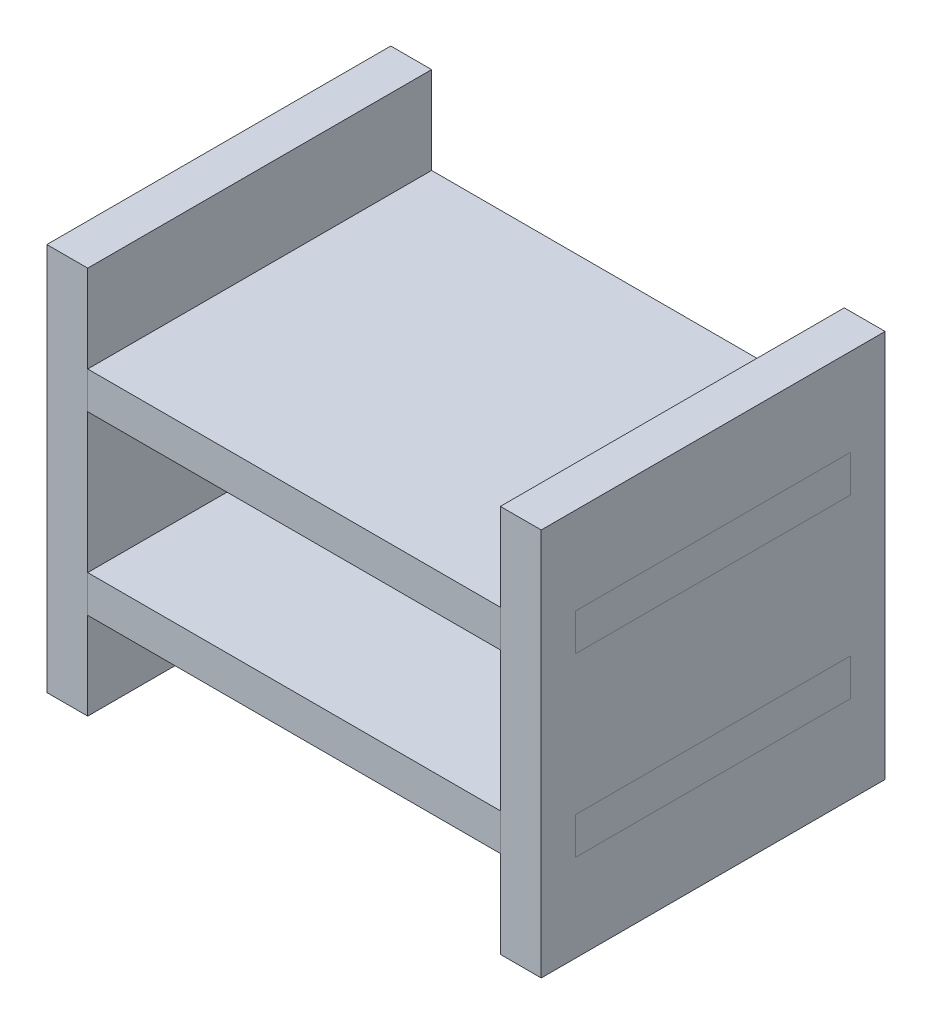
SolidWorks part; units mm, degrees
ref_plane "Front" through (0, 0, 0) normal (0, 0, 1) x (1, 0, 0)
ref_plane "Top" through (0, 0, 0) normal (0, 1, 0) x (1, 0, 0)
ref_plane "Right" through (0, 0, 0) normal (1, 0, 0) x (0, 0, -1)
sketch "Sketch2" plane through (0, 0, 0) normal (0, 1, 0) x (1, 0, 0)
  line L1 (-15, 12.5) -> (15, 12.5)
  line L2 (-15, 12.5) -> (-15, -12.5)
  line L3 (-15, -12.5) -> (15, -12.5)
  line L4 (15, 12.5) -> (15, -12.5)
  line L5 (-15, 12.5) -> (15, -12.5) construction
  line L6 (-15, -12.5) -> (15, 12.5) construction
  line L7 (-15, 10) -> (-17.97, 10)
  line L8 (-15, 10) -> (-15, -10)
  line L9 (-15, -10) -> (-17.97, -10)
  line L10 (-17.97, 10) -> (-17.97, -10)
  line L11 (-15, 10) -> (-17.97, -10) construction
  line L12 (-15, -10) -> (-17.97, 10) construction
  line L13 (15, 10) -> (17.97, 10)
  line L14 (15, 10) -> (15, -10)
  line L15 (15, -10) -> (17.97, -10)
  line L16 (17.97, 10) -> (17.97, -10)
  line L17 (15, 10) -> (17.97, -10) construction
  line L18 (15, -10) -> (17.97, 10) construction
  point P4 (0, 0)
  point P5 (0, 0)
  point P11 (-16.485, 0)
  point P16 (16.485, 0)
  dimension "D1" = 2.97
  dimension "D2" = 30
  dimension "D3" = 25
  dimension "D4" = 20
extrude "Boss-Extrude3" add sketch "Sketch2" along normal blind 2.69 contours L4 L1 L2 L3 | L7 L10 L9 L2 | L16 L13 L4 L15 region at (0, 0, 0) region at (-16.485, 0, 0) region at (16.485, 0, 0)
extrude "Boss-Extrude4" add sketch "Sketch2<3>" along normal blind 2.69 from offset 12.8175 separate body contours L7 L10 L9 L2 | L4 L1 L2 L3 | L16 L13 L4 L15 region at (0, 0, 0) region at (-16.485, 0, 0) region at (16.485, 0, 0)
sketch "Sketch2<3>" plane through (0, 0, 0) normal (0, 1, 0) x (1, 0, 0) same geometry as "Sketch2"
sketch "Sketch4" plane through (15, 0, 0) normal (1, 0, 0) x (0, 0, -1)
  line L0 (0, 50) -> (0, -50) construction
  line L1 (12.5, -6.35) -> (-12.5, -6.35)
  line L2 (12.5, -6.35) -> (12.5, 21.8575)
  line L3 (12.5, 21.8575) -> (-12.5, 21.8575)
  line L4 (-12.5, -6.35) -> (-12.5, 21.8575)
  line L5 (12.5, -6.35) -> (-12.5, 21.8575) construction
  line L6 (12.5, 21.8575) -> (-12.5, -6.35) construction
  line L7 (-12.5, 15.5075) -> (-12.5, 12.8175) construction
  line L8 (-10, 15.5075) -> (-12.5, 15.5075) construction
  line L9 (0, 12.8175) -> (0, 2.69) construction
  line L10 (10, 12.8175) -> (-10, 12.8175) construction
  line L11 (10, 2.69) -> (-10, 2.69) construction
  line L12 (-10, 15.5075) -> (-10, 12.8175) construction
  line L13 (-10, 15.5075) -> (10, 15.5074)
  line L14 (-10, 15.5075) -> (-10, 12.8175)
  line L15 (-10, 12.8175) -> (10, 12.8175)
  line L16 (10, 15.5074) -> (10, 12.8175)
  line L17 (-10, 15.5075) -> (10, 12.8175) construction
  line L18 (-10, 12.8175) -> (10, 15.5074) construction
  line L19 (10, 15.5075) -> (-10, 15.5075) construction
  line L21 (10, 2.69) -> (-10, 2.69)
  line L22 (10, 2.69) -> (10, 0)
  line L23 (10, 0) -> (-10, 0)
  line L24 (-10, 2.69) -> (-10, 0)
  line L25 (10, 2.69) -> (-10, 0) construction
  line L26 (10, 0) -> (-10, 2.69) construction
  point P0 (0, 7.7537)
  point P19 (0, 7.7537)
  point P22 (0, 14.1624)
  point P32 (0, 1.345)
  dimension "D1" = 6.35
extrude "Boss-Extrude5" add sketch "Sketch4" along normal up to surface (2.97 mm away) separate body up to face at (17.97, 14.1624, 0)
mirror "Mirror1" about plane through (0, 0, 0) normal (1, 0, 0) of bodies 105
